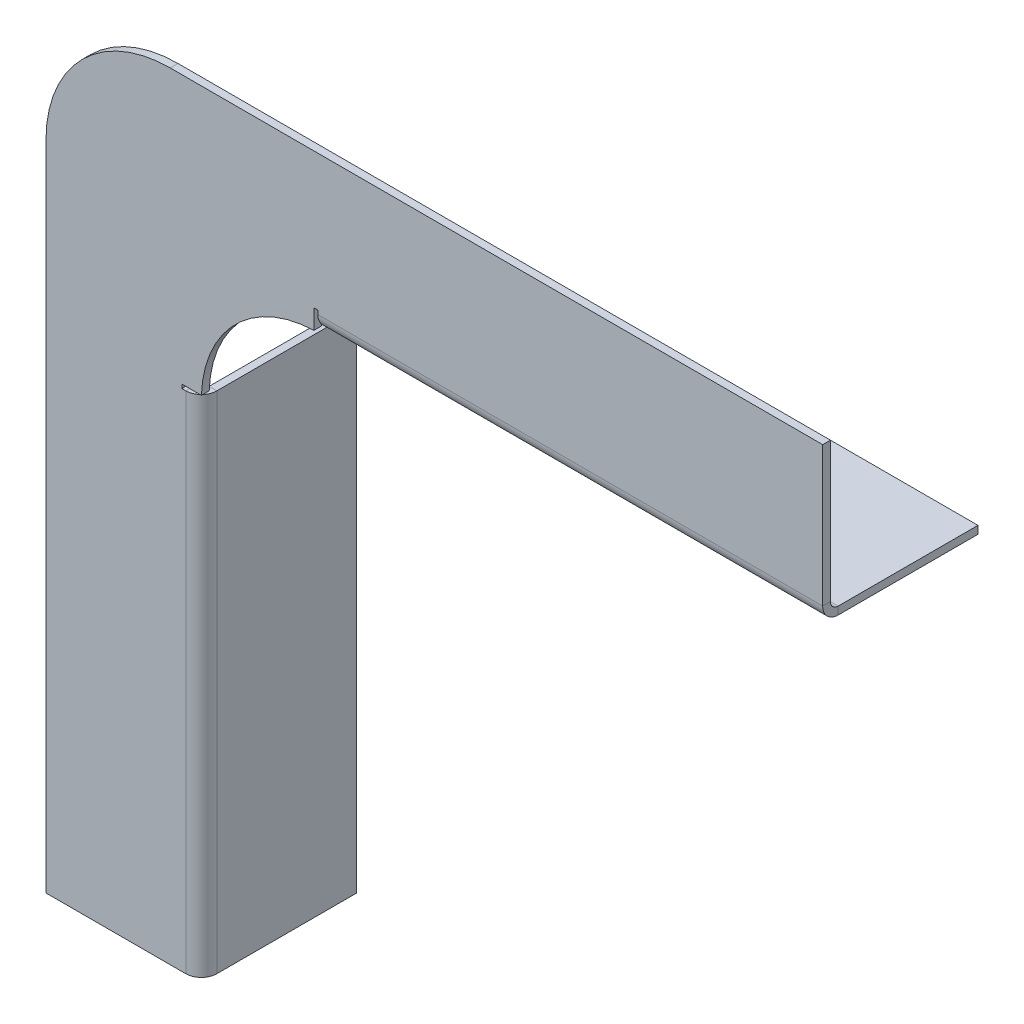
SolidWorks part; units mm, degrees
note: The reader was unsure of these and kept them because the rebuilt part matched: flange length of "Edge-Flange1".
ref_plane "Front Plane" through (0, 0, 0) normal (0, 0, 1) x (1, 0, 0)
ref_plane "Top Plane" through (0, 0, 0) normal (0, 1, 0) x (1, 0, 0)
ref_plane "Right Plane" through (0, 0, 0) normal (1, 0, 0) x (0, 0, -1)
sketch "Sketch1" plane through (0, 0, 0) normal (0, 0, 1) x (1, 0, 0)
  line L0 (-16, 0) -> (-16, -84)
  line L1 (-16, -84) -> (4, -84)
  line L2 (4, -84) -> (4, -19)
  line L3 (0, 16) -> (84, 16)
  line L4 (84, 16) -> (84, -4)
  line L5 (84, -4) -> (19, -4)
  arc A1 (0, 16) -> (-16, 0) centre (0, 0) ccw
  arc A2 (19, -4) -> (4, -19) centre (19, -19) ccw
  dimension "D1" = 20
  dimension "D4" = 30
  dimension "D5" = 20
  dimension "D6" = 16
  dimension "D2" = 84
  dimension "D3" = 84
base flange "Base-Flange1" sketch "Sketch1" thickness 1 reverse thickness direction no parameters "D1"=1
edge flange "Edge-Flange1" sketch "Sketch8" flange profiles "Sketch8", "Sketch10" flange angle 90 flange length 20 flange position material inside bend radius 1 thickness 1 relief rectangular parameters "D6"=10, "D8"=1
sketch "Sketch8" plane through (0, -4, -1) normal (0, -1, 0) x (-1, 0, 0)
  line L0 (-19, 0) -> (-84, 0) construction
  line L1 (-19, 0) -> (-84, 0)
  line L2 (-84, 0) -> (-84, 19)
  line L3 (-84, 19) -> (-19, 19)
  line L4 (-19, 19) -> (-19, 0)
sketch "Sketch10" plane through (4, 0, -1) normal (1, 0, 0) x (0, -1, 0)
  line L0 (84, 0) -> (19, 0) construction
  line L1 (84, 0) -> (19, 0)
  line L2 (19, 0) -> (19, 19)
  line L3 (19, 19) -> (84, 19)
  line L4 (84, 19) -> (84, 0)
bend "EdgeBend1" bend radius 1 bend angle 90 parameters "D5"=1
bend "EdgeBend2" bend radius 1 bend angle 90 parameters "D5"=3
sketch "Bend-Lines1" [suppressed] plane through (0, 0, 0) normal (0, 1, 0) x (1, 0, 0)
sketch "Bounding-Box1" [suppressed] plane through (0, 0, 0) normal (0, 1, 0) x (1, 0, 0)
sheet metal parameters "Sheet-Metal1" thickness 1 parameters "D1"=1
flat pattern "Flat-Pattern1" [suppressed]
sketch "Bend-Lines2" plane through (0, 0, 0) normal (0, 1, 0) x (1, 0, 0)
sketch3d "Bounding-Box2" [suppressed]
  line L0 (-99, -99, 0) -> (-99, 15, 0) construction
  line L1 (15, -99, 0) -> (15, 15, 0) construction
  line L2 (-99, -99, 0) -> (15, -99, 0) construction
  line L3 (-99, 15, 0) -> (15, 15, 0) construction
sheet metal parameters "Sheet-Metal2" thickness 1 parameters "D1"=1
flat pattern "Flat-Pattern1"
sketch "Bend-Lines2" plane through (0, 0, 0) normal (0, 0, 1) x (1, 0, 0)
  line L0 (19, -3.1781) -> (84, -3.1781) construction
  line L1 (19, -3.1781) -> (84, -3.1781) construction
  line L2 (3.1781, -84) -> (3.1781, -19) construction
  line L3 (3.1781, -84) -> (3.1781, -19) construction
sketch3d "Bounding-Box2" [suppressed]
  line L0 (84, -84, 0) -> (84, 16, 0) construction
  line L1 (-16, -84, 0) -> (-16, 16, 0) construction
  line L2 (84, -84, 0) -> (-16, -84, 0) construction
  line L3 (84, 16, 0) -> (-16, 16, 0) construction
bend of the flat pattern "Flatten-<EdgeBend1>1"
bend of the flat pattern "Flatten-<EdgeBend2>1"
